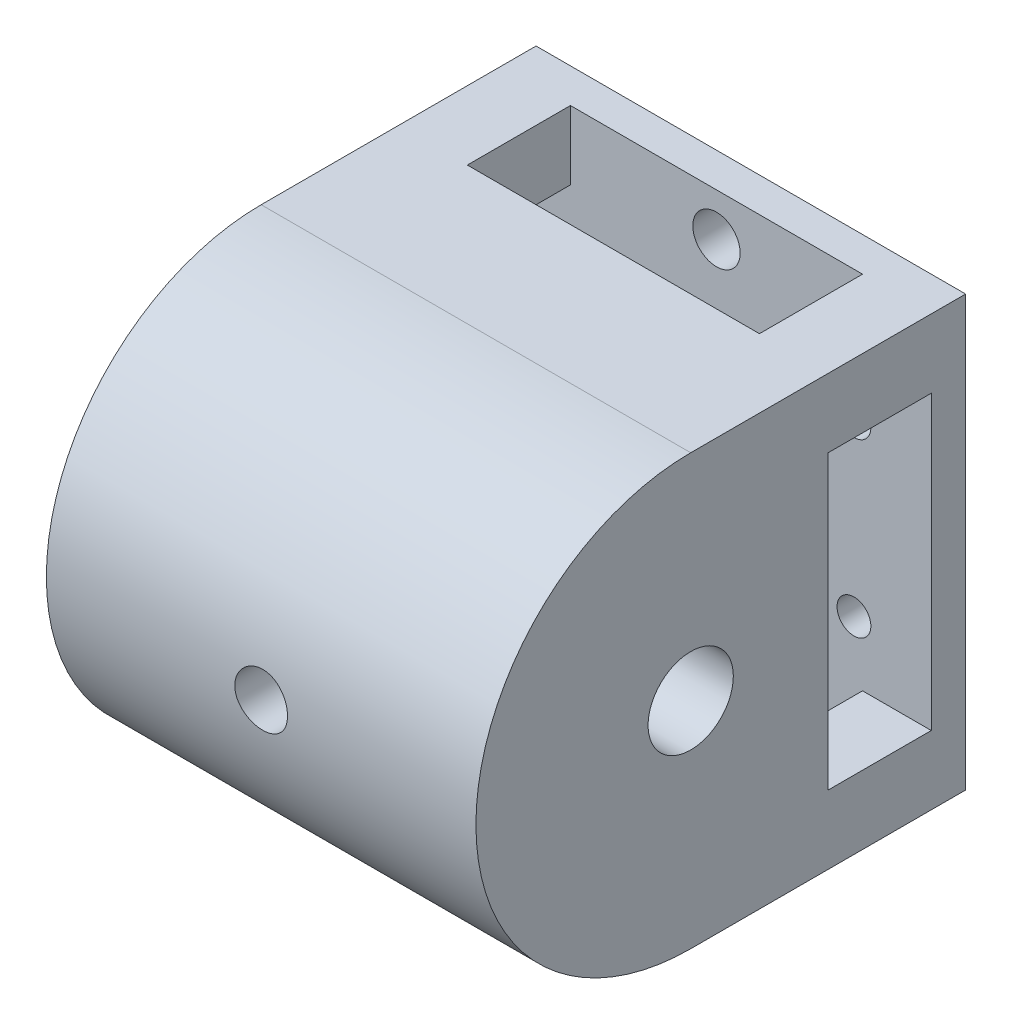
SolidWorks part; units mm, degrees
material "PLA"
ref_plane "Front Plane" through (0, 0, 0) normal (0, 0, 1) x (1, 0, 0)
ref_plane "Top Plane" through (0, 0, 0) normal (0, 1, 0) x (1, 0, 0)
ref_plane "Right Plane" through (0, 0, 0) normal (1, 0, 0) x (0, 0, -1)
sketch "Sketch1" plane through (0, 0, 0) normal (1, 0, 0) x (0, 0, -1)
  line L0 (0, 15.875) -> (20.32, 15.875)
  line L1 (20.32, 15.875) -> (20.32, -15.875)
  line L2 (20.32, -15.875) -> (0, -15.875)
  circle A0 centre (0, 0) radius 15.875
  circle A1 centre (0, 0) radius 3.15
  dimension "D1" = 31.75
  dimension "D3" = 6.3
  dimension "D2" = 20.32
extrude "Boss-Extrude1" add sketch "Sketch1" along normal blind 31.75 contours A0 | A0 L2 L1 L0 region at (0, 15.498, -10.16) region at (0, 10.9078, -10.9078)
sketch "Sketch2" plane through (0, 0, -20.32) normal (0, 0, -1) x (-1, 0, 0)
  line L0 (-15.875, 0) -> (-15.875, 6.1274) construction
  line L1 (-15.875, 0) -> (-7.897, 0) construction
  line L4 (0, -15.875) -> (0, 15.875)
  line L5 (0, 15.875) -> (-31.75, 15.875)
  line L6 (-31.75, 15.875) -> (-31.75, -15.875)
  line L7 (-31.75, -15.875) -> (0, -15.875)
  line L8 (0, -15.875) -> (0, 15.875)
  line L9 (0, 15.875) -> (-31.75, 15.875)
  line L10 (-31.75, 15.875) -> (-31.75, -15.875)
  line L11 (-31.75, -15.875) -> (0, -15.875)
  circle A0 centre (-15.875, 0) radius 15.875 construction
  circle A1 centre (-26.035, 6.35) radius 1.25
  circle A2 centre (-5.715, 6.35) radius 1.25
  circle A3 centre (-5.715, -6.35) radius 1.25
  circle A4 centre (-26.035, -6.35) radius 1.25
  point P2 (-15.875, 0)
  point P6 (-15.875, 15.875)
  dimension "D2" = 31.75
  dimension "D3" = 2.5
  dimension "D4" = 12.7
  dimension "D5" = 20.32
  dimension "D1" = 0
sketch "Sketch4" plane through (0, 0, 0) normal (-1, 0, 0) x (0, 0, 1)
  line L0 (-17.78, 15.875) -> (-17.78, -15.875)
  line L1 (-10.16, 15.875) -> (-10.16, -15.875)
  line L2 (0, 15.875) -> (-20.32, 15.875) construction
  line L3 (0, 15.875) -> (-20.32, 15.875)
  line L4 (-20.32, 15.875) -> (-20.32, -15.875)
  line L5 (-20.32, -15.875) -> (0, -15.875)
  line L6 (0, 15.875) -> (-20.32, 15.875)
  line L7 (-20.32, 15.875) -> (-20.32, -15.875)
  line L8 (-20.32, -15.875) -> (0, -15.875)
  line L9 (-10.16, 10.795) -> (-17.78, 10.795)
  line L10 (-17.78, -10.795) -> (-10.16, -10.795)
  arc A1 (0, -15.875) -> (0, 15.875) centre (0, 0) ccw
  arc A2 (0, -15.875) -> (0, 15.875) centre (0, 0) ccw
  dimension "D2" = 2.54
  dimension "D3" = 7.62
  dimension "D4" = 5.08
  dimension "D5" = 5.08
  dimension "D1" = 0
extrude "Cut-Extrude1" cut sketch "Sketch4" against normal through all contours L0 L10 L1 L9 region at (0, 0, -13.97)
extrude "Cut-Extrude2" cut sketch "Sketch2" against normal up to surface (2.54 mm away) contours A1 | A2 | A3 | A4 region at (26.035, 6.35, -20.32) region at (5.715, 6.35, -20.32) region at (5.715, -6.35, -20.32) region at (26.035, -6.35, -20.32) up to face at (15.875, 0, -17.78)
sketch "Sketch5" plane through (0, 15.875, 0) normal (0, 1, 0) x (1, 0, 0)
  line L0 (5.08, 17.78) -> (5.08, 10.16)
  line L1 (26.67, 10.16) -> (26.67, 17.78)
  line L4 (0, 17.78) -> (0, 10.16)
  line L5 (0, 10.16) -> (31.75, 10.16)
  line L6 (31.75, 10.16) -> (31.75, 17.78)
  line L7 (31.75, 17.78) -> (0, 17.78)
  line L8 (0, 17.78) -> (0, 10.16)
  line L9 (0, 10.16) -> (31.75, 10.16)
  line L10 (31.75, 10.16) -> (31.75, 17.78)
  line L11 (31.75, 17.78) -> (0, 17.78)
  dimension "D2" = 5.08
  dimension "D3" = 5.08
  dimension "D1" = 0
extrude "Cut-Extrude3" cut sketch "Sketch5" against normal through all contours L1 L11 L0 L9 region at (15.875, 15.875, -13.97)
sketch "Sketch6" plane through (0, 0, -20.32) normal (0, 0, -1) x (-1, 0, 0)
  line L0 (0, 0) -> (-5.8796, 0) construction
  line L4 (0, -15.875) -> (0, 15.875)
  line L5 (0, 15.875) -> (-31.75, 15.875)
  line L6 (-31.75, 15.875) -> (-31.75, -15.875)
  line L7 (-31.75, -15.875) -> (0, -15.875)
  line L8 (0, -15.875) -> (0, 15.875)
  line L9 (0, 15.875) -> (-31.75, 15.875)
  line L10 (-31.75, 15.875) -> (-31.75, -15.875)
  line L11 (-31.75, -15.875) -> (0, -15.875)
  circle A0 centre (-15.875, 12.7) radius 1.75
  circle A1 centre (-15.875, -12.7) radius 1.75
  point P6 (-15.875, 15.875)
  dimension "D1" = 3.5
  dimension "D2" = 12.7
  dimension "D3" = 0
extrude "Cut-Extrude4" cut sketch "Sketch6" against normal up to surface (2.54 mm away) contours A0 | A1 region at (15.875, 12.7, -20.32) region at (15.875, -12.7, -20.32) up to face at (26.035, -5.1, -17.78)
ref_plane "Plane1" through (0, 0, 50.8) normal (0, 0, 1) x (1, 0, 0)
sketch "Sketch7" plane through (0, 0, 50.8) normal (0, 0, 1) x (1, 0, 0)
  line L12 (0, -10.795) -> (5.08, -10.795)
  line L13 (5.08, -10.795) -> (5.08, -15.875)
  line L14 (5.08, -15.875) -> (26.67, -15.875)
  line L15 (26.67, -15.875) -> (26.67, -10.795)
  line L16 (26.67, -10.795) -> (31.75, -10.795)
  line L17 (31.75, -10.795) -> (31.75, 10.795)
  line L18 (31.75, 10.795) -> (26.67, 10.795)
  line L19 (26.67, 10.795) -> (26.67, 15.875)
  line L20 (26.67, 15.875) -> (5.08, 15.875)
  line L21 (5.08, 15.875) -> (5.08, 10.795)
  line L22 (5.08, 10.795) -> (0, 10.795)
  line L23 (0, 10.795) -> (0, -10.795)
  line L24 (0, -10.795) -> (5.08, -10.795)
  line L25 (5.08, -10.795) -> (5.08, -15.875)
  line L26 (5.08, -15.875) -> (26.67, -15.875)
  line L27 (26.67, -15.875) -> (26.67, -10.795)
  line L28 (26.67, -10.795) -> (31.75, -10.795)
  line L29 (31.75, -10.795) -> (31.75, 10.795)
  line L30 (31.75, 10.795) -> (26.67, 10.795)
  line L31 (26.67, 10.795) -> (26.67, 15.875)
  line L32 (26.67, 15.875) -> (5.08, 15.875)
  line L33 (5.08, 15.875) -> (5.08, 10.795)
  line L34 (5.08, 10.795) -> (0, 10.795)
  line L35 (0, 10.795) -> (0, -10.795)
  circle A0 centre (15.875, 0) radius 1.95
  dimension "D2" = 3.9
  dimension "D1" = 0
extrude "Cut-Extrude5" cut sketch "Sketch7" against normal up to surface (47.65 mm away) contours A0 region at (15.875, 0, 50.8) up to face at (31.75, 0, -3.15)
